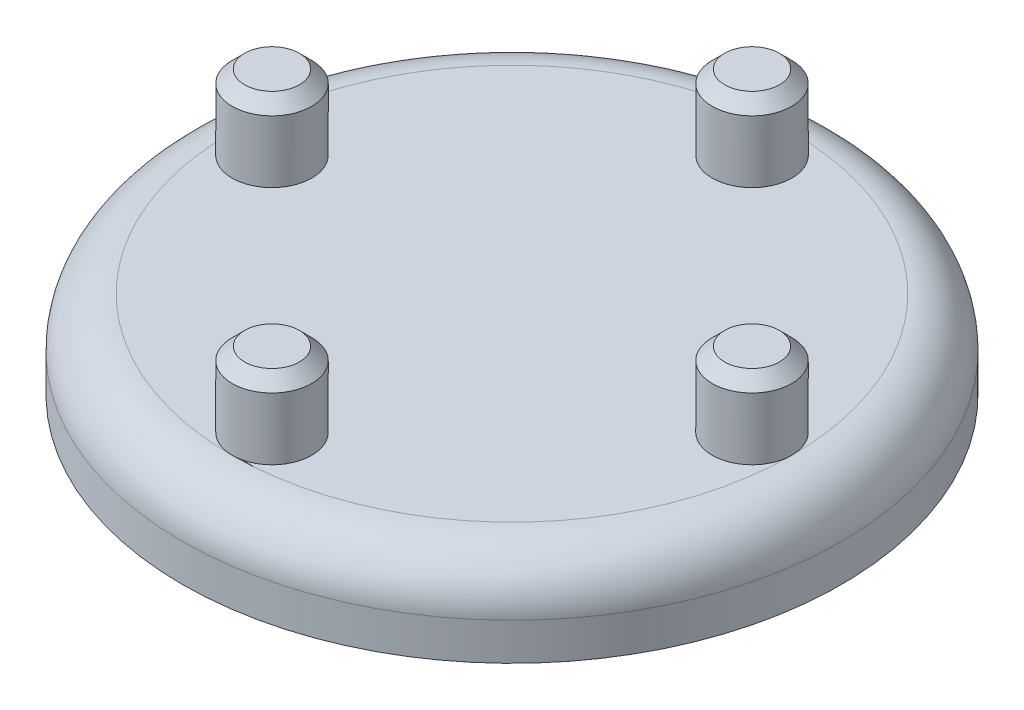
SolidWorks part; units mm, degrees
ref_plane "Front Plane" through (0, 0, 0) normal (0, 0, 1) x (1, 0, 0)
ref_plane "Top Plane" through (0, 0, 0) normal (0, 1, 0) x (1, 0, 0)
ref_plane "Right Plane" through (0, 0, 0) normal (1, 0, 0) x (0, 0, -1)
sketch "Sketch1" plane through (0, 0, 0) normal (0, 1, 0) x (1, 0, 0)
  circle A0 centre (0, 0) radius 26.5
  circle A1 centre (-13.6472, 13.6472) radius 3.75
  circle A2 centre (0, 19.3) radius 3.2
  circle A3 centre (13.6472, 13.6472) radius 3.75
  circle A4 centre (19.3, 0) radius 3.2
  circle A5 centre (13.6472, -13.6472) radius 3.75
  circle A6 centre (0, -19.3) radius 3.2
  circle A7 centre (-13.6472, -13.6472) radius 3.75
  circle A8 centre (-19.3, 0) radius 3.2
  circle A9 centre (0, 0) radius 6.25
  circle A10 centre (0, 19.3) radius 3.15
  circle A11 centre (0, -19.3) radius 3.15
  circle A12 centre (0, 19.3) radius 3.15
  circle A13 centre (0, -19.3) radius 3.15
  point P5 (0, 0)
  circle B0 centre (0, 19.3) radius 3.15
  circle B1 centre (0, -19.3) radius 3.15
  circle B2 centre (-19.3, 0) radius 3.15
  circle B3 centre (-13.6472, -13.6472) radius 3.15
  circle B4 centre (-13.6472, 13.6472) radius 3.15
  circle B5 centre (13.6472, -13.6472) radius 3.15
  circle B6 centre (19.3, 0) radius 3.15
  circle B7 centre (13.6472, 13.6472) radius 3.15
  circle B8 centre (-19.3, 0) radius 3.15
  circle B9 centre (19.3, 0) radius 3.15
sketch_block_instance "Block2-9"
sketch_block "Block2" parameters "D2"=3.9779, "D1"=8
extrude "Boss-Extrude1" add sketch "Sketch1" along normal blind 7 contours A0
sketch "Sketch2" plane through (0, 0, 0) normal (0, -1, 0) x (1, 0, 0)
  circle A1 centre (0, 0) radius 6.1
extrude "Boss-Extrude4" add sketch "Sketch1<12>" along normal blind 6 from surface contours A4 | A8 starting at face at (0, 7, 26.5)
sketch "Sketch1<12>" plane through (0, 0, 0) normal (0, 1, 0) x (1, 0, 0) same geometry as "Sketch1"
fillet "Fillet1" radius 4 1 edges at (0, 7, 26.5)
chamfer "Chamfer1" distance 1 angle 45 2 edges at (-19.3, 13, 3.2) (19.3, 13, 3.2)
extrude "Boss-Extrude5" add sketch "Sketch1<16>" along normal blind 6 from surface contours A2 starting at face at (0, 7, 1.6)
sketch "Sketch1<16>" plane through (0, 0, 0) normal (0, 1, 0) x (1, 0, 0) same geometry as "Sketch1"
extrude "Boss-Extrude6" add sketch "Sketch1<17>" along normal blind 6 from surface contours A6 starting at face at (0, 7, -3.17)
sketch "Sketch1<17>" plane through (0, 0, 0) normal (0, 1, 0) x (1, 0, 0) same geometry as "Sketch1"
chamfer "Chamfer2" distance 1 angle 45 2 edges at (0, 13, -16.1) (0, 13, 22.5)
